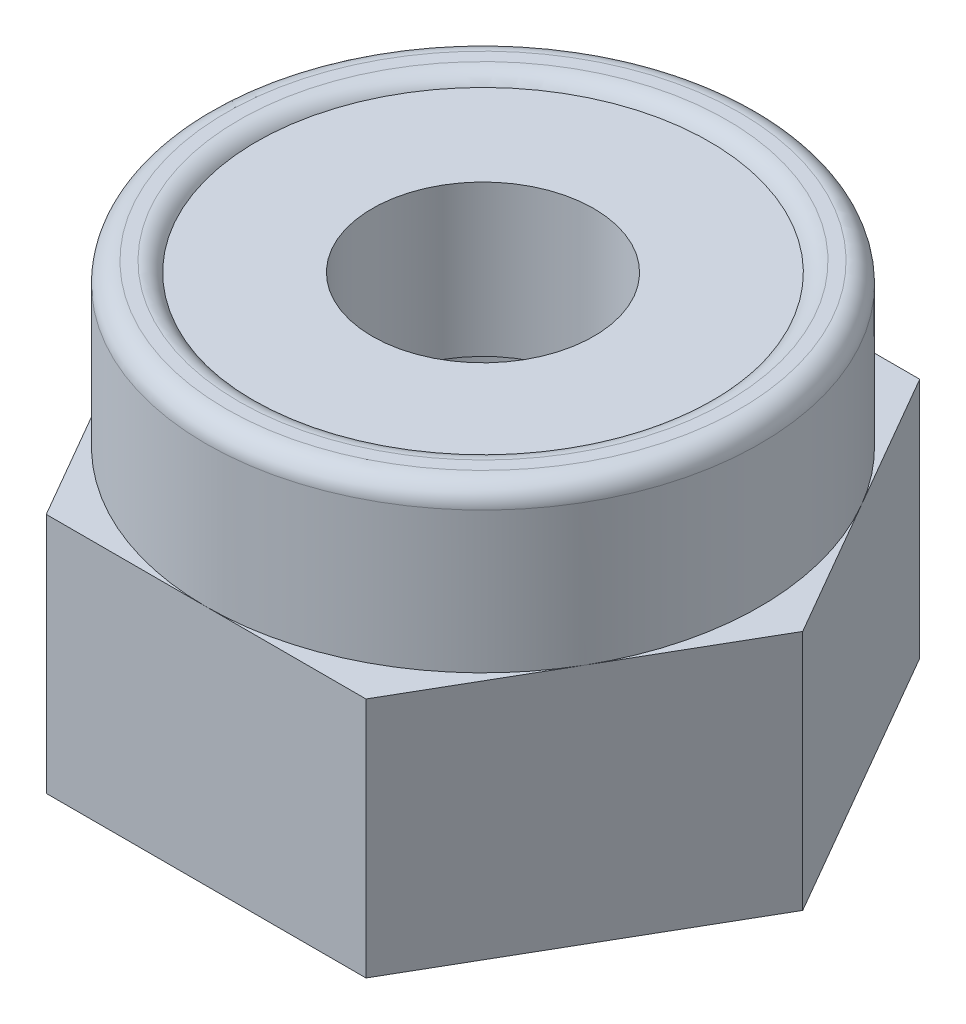
SolidWorks part; units mm, degrees
material "acero"
ref_plane "Alzado" through (0, 0, 0) normal (0, 0, 1) x (1, 0, 0)
ref_plane "Planta" through (0, 0, 0) normal (0, 1, 0) x (1, 0, 0)
ref_plane "Vista lateral" through (0, 0, 0) normal (1, 0, 0) x (0, 0, -1)
sketch "Croquis1" plane through (0, 0, 0) normal (0, 1, 0) x (1, 0, 0)
  line L1 (-1.5877, 2.75) -> (-3.1754, 0)
  line L2 (-3.1754, 0) -> (-1.5877, -2.75)
  line L3 (-1.5877, -2.75) -> (1.5877, -2.75)
  line L4 (1.5877, -2.75) -> (3.1754, 0)
  line L5 (3.1754, 0) -> (1.5877, 2.75)
  line L6 (1.5877, 2.75) -> (-1.5877, 2.75)
  circle A0 centre (0, 0) radius 2.75 construction
  circle A1 centre (0, 0) radius 1.25
  dimension "D1" = 2.5
  dimension "D2" = 5.5
extrude "Saliente-Extruir1" add sketch "Croquis1" along normal blind 2.4
sketch "Croquis2" plane through (0, 2.4, 0) normal (0, 1, 0) x (1, 0, 0)
  line L0 (3.1754, 0) -> (1.5877, 2.75) construction
  circle A0 centre (0, 0) radius 2.75
  circle A1 centre (0, 0) radius 1.1
  dimension "D1" = 2.2
extrude "Saliente-Extruir2" add sketch "Croquis2" along normal blind 1.6
sketch "Croquis4" plane through (0, 4, 0) normal (0, 1, 0) x (1, 0, 0)
  circle A0 centre (0, 0) radius 1.1 construction
  circle A1 centre (0, 0) radius 1.1
  circle A2 centre (0, 0) radius 2.25
  dimension "D1" = 4.5
extrude "Cortar-Extruir1" cut sketch "Croquis4" against normal blind 0.1
fillet "Redondeo1" radius 0.2 2 edges at (0, 4, 2.75) (0, 4, 2.25)
